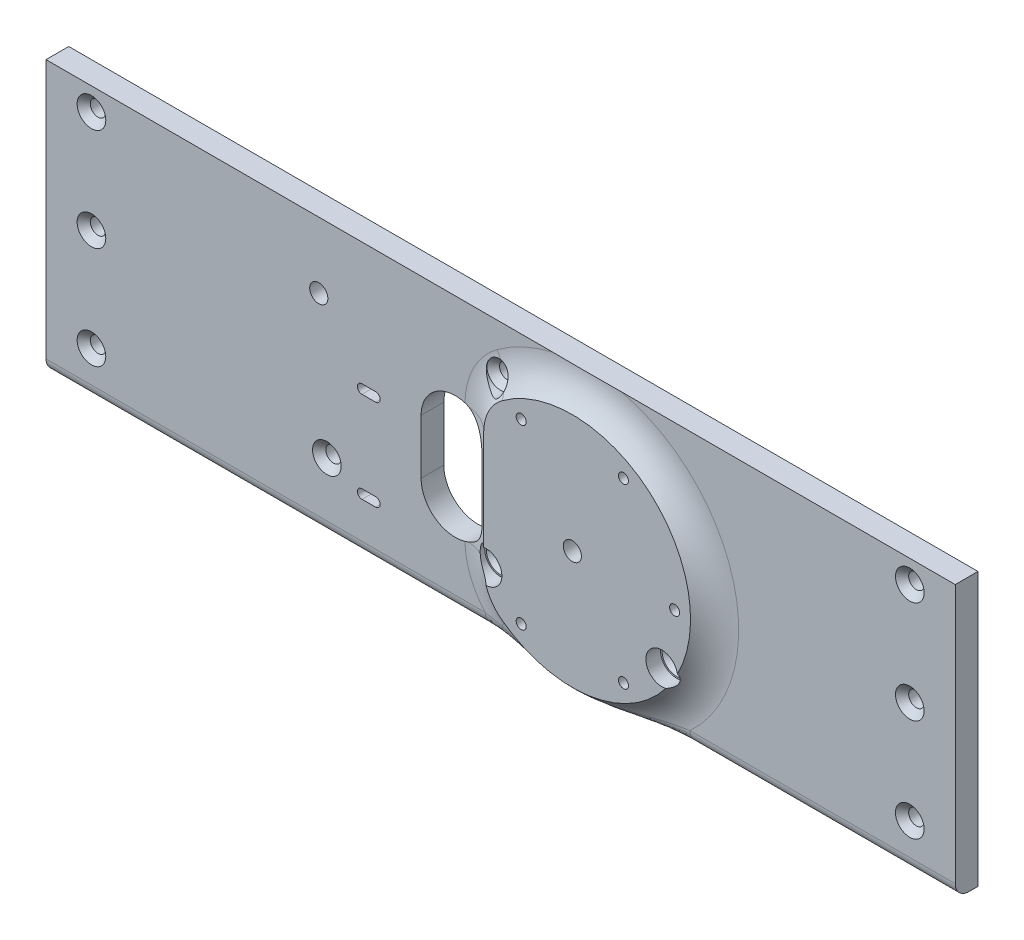
SolidWorks part; units mm, degrees
ref_plane "Front Plane" through (0, 0, 0) normal (0, 0, 1) x (1, 0, 0)
ref_plane "Top Plane" through (0, 0, 0) normal (0, 1, 0) x (1, 0, 0)
ref_plane "Right Plane" through (0, 0, 0) normal (1, 0, 0) x (0, 0, -1)
sketch "Sketch1" plane through (0, 0, 0) normal (0, 0, 1) x (1, 0, 0)
  line L0 (90, 33.5) -> (90, 21.5) construction
  line L1 (0, 0) -> (200, 0)
  line L2 (0, 0) -> (0, 60)
  line L3 (0, 60) -> (200, 60)
  line L4 (200, 0) -> (200, 60)
  line L5 (97.5, 33.5) -> (97.5, 21.5)
  line L6 (82.5, 33.5) -> (82.5, 21.5)
  line L7 (90, 27.5) -> (119, 27.5) construction
  circle A0 centre (119, 27.5) radius 26.5 construction
  circle A2 centre (119, 27.5) radius 2
  circle A3 centre (60, 45.5) radius 2
  arc A4 (97.5, 33.5) -> (82.5, 33.5) centre (90, 33.5) ccw
  arc A5 (82.5, 21.5) -> (97.5, 21.5) centre (90, 21.5) ccw
  arc A6 (142.525, 27.5) -> (140.475, 27.5) centre (141.5, 27.5) ccw construction
  arc A7 (129.225, 8.0144) -> (131.275, 8.0144) centre (130.25, 8.0144) ccw construction
  arc A8 (106.725, 8.0144) -> (108.775, 8.0144) centre (107.75, 8.0144) ccw construction
  arc A9 (106.725, 46.9856) -> (108.775, 46.9856) centre (107.75, 46.9856) ccw construction
  arc A10 (131.275, 46.9856) -> (129.225, 46.9856) centre (130.25, 46.9856) ccw construction
  arc A11 (142.525, 27.5) -> (140.475, 27.5) centre (141.5, 27.5) ccw construction
  arc A12 (129.225, 8.0144) -> (131.275, 8.0144) centre (130.25, 8.0144) ccw construction
  arc A13 (106.725, 8.0144) -> (108.775, 8.0144) centre (107.75, 8.0144) ccw construction
  arc A14 (106.725, 46.9856) -> (108.775, 46.9856) centre (107.75, 46.9856) ccw construction
  arc A15 (131.275, 46.9856) -> (129.225, 46.9856) centre (130.25, 46.9856) ccw construction
  circle A16 centre (130.25, 46.9856) radius 1.1
  circle A17 centre (141.5, 27.5) radius 1.1
  circle A18 centre (130.25, 8.0144) radius 1.1
  circle A19 centre (107.75, 8.0144) radius 1.1
  circle A20 centre (107.75, 46.9856) radius 1.1
  point P8 (90, 27.5)
  dimension "D1" = 4
  dimension "D2" = 4
  dimension "D5" = 53
  dimension "D9" = 1
  dimension "D12" = 5
  dimension "D13" = 2.2
  dimension "D3" = 59
  dimension "D4" = 18
  dimension "D6" = 60
  dimension "D7" = 200
  dimension "D8" = 60
  dimension "D10" = 12
  dimension "D11" = 15
extrude "Boss-Extrude1" add sketch "Sketch1" along normal blind 5
sketch "Sketch3" plane through (0, 0, 5) normal (0, 0, 1) x (1, 0, 0)
  line L0 (99.5, 40.3744) -> (99.5, 14.6256)
  line L1 (97.5, 21.5) -> (97.5, 33.5) construction
  arc A0 (103.5625, 6.5791) -> (103.5625, 48.4209) centre (119, 27.5) ccw
  arc A1 (99.5, 40.3744) -> (103.5625, 48.4209) centre (109.5, 40.3744) cw
  arc A2 (99.5, 14.6256) -> (103.5625, 6.5791) centre (109.5, 14.6256) ccw
  circle A3 centre (119, 27.5) radius 2 construction
  circle A4 centre (107.75, 8.0144) radius 1.1 construction
  circle A5 centre (130.25, 8.0144) radius 1.1 construction
  circle A6 centre (141.5, 27.5) radius 1.1 construction
  circle A7 centre (130.25, 46.9856) radius 1.1 construction
  circle A8 centre (107.75, 46.9856) radius 1.1 construction
  circle A9 centre (119, 27.5) radius 2
  circle A10 centre (107.75, 8.0144) radius 1.1
  circle A11 centre (130.25, 8.0144) radius 1.1
  circle A12 centre (141.5, 27.5) radius 1.1
  circle A13 centre (130.25, 46.9856) radius 1.1
  circle A14 centre (107.75, 46.9856) radius 1.1
  dimension "D1" = 10
  dimension "D3" = 26
  dimension "D2" = 2
extrude "Boss-Extrude2" add sketch "Sketch3" along normal up to surface (3.23 mm away)
fillet "Fillet1" radius 10 4 edges at (100.5732, 10.1187, 5) (99.5, 27.5, 5) (100.5732, 44.8813, 5) (145, 27.5, 5)
sketch "Sketch4" plane through (0, 0, 5) normal (0, 0, 1) x (1, 0, 0)
  line L0 (69.5, 32) -> (72.5, 32) construction
  line L1 (69.5, 33) -> (72.5, 33)
  line L2 (69.5, 31) -> (72.5, 31)
  line L3 (69.5, 12) -> (72.5, 12) construction
  line L4 (69.5, 13) -> (72.5, 13)
  line L5 (69.5, 11) -> (72.5, 11)
  line L6 (0, 0) -> (100.1154, 0) construction
  line L7 (82.5, 33.5) -> (82.5, 21.5) construction
  arc A0 (69.5, 33) -> (69.5, 31) centre (69.5, 32) ccw
  arc A1 (72.5, 31) -> (72.5, 33) centre (72.5, 32) ccw
  arc A2 (69.5, 13) -> (69.5, 11) centre (69.5, 12) ccw
  arc A3 (72.5, 11) -> (72.5, 13) centre (72.5, 12) ccw
  point P2 (71, 32)
  point P7 (71, 12)
  dimension "D1" = 3
  dimension "D2" = 20
  dimension "D3" = 12
  dimension "D4" = 10
  dimension "D5" = 2
extrude "Cut-Extrude1" cut sketch "Sketch4" against normal blind 10
sketch "Sketch8" plane through (0, 0, 5) normal (0, 0, 1) x (1, 0, 0)
  line L0 (10, 55) -> (190, 55) construction
  line L1 (100, 50) -> (100, 60) construction
  line L2 (111.4748, 60) -> (0, 60) construction
  line L3 (61.7843, 15) -> (100, 15) construction
  line L4 (100, 15) -> (100, 50) construction
  line L5 (100, 15) -> (138.6766, 15) construction
  circle A0 centre (190, 10) radius 3 construction
  circle A1 centre (190, 32.5) radius 3 construction
  circle A2 centre (190, 55) radius 3 construction
  circle A3 centre (10, 10) radius 3 construction
  circle A4 centre (10, 32.5) radius 3 construction
  circle A5 centre (10, 55) radius 3 construction
  circle A6 centre (190, 10) radius 3
  circle A7 centre (190, 32.5) radius 3
  circle A8 centre (190, 55) radius 3
  circle A9 centre (10, 10) radius 3
  circle A10 centre (10, 32.5) radius 3
  circle A11 centre (10, 55) radius 3
  circle A12 centre (138.6766, 15) radius 2.1 construction
  circle A13 centre (61.7843, 15) radius 3 construction
  circle A14 centre (138.6766, 15) radius 2.1
  circle A15 centre (61.7843, 15) radius 3
  circle A16 centre (100, 15) radius 3
  circle A17 centre (100, 50) radius 3 construction
  circle A18 centre (100, 50) radius 2.1 construction
  circle A19 centre (100, 50) radius 2.1
  point P31 (0, 0)
  point P32 (101.1096, 53.6973)
  point P36 (100, 49.6918)
hole_wizard "CSK for M3 Flat Head Machine Screw1" positions "3DSketch1" profile "Sketch9" countersink size "M3" standard "ANSI Metric" end condition through all
sketch3d "3DSketch1"
  line L0 (61.7843, 15, 5) -> (100, 15, 5) construction
  line L1 (100, 15, 5) -> (100, 50, 5) construction
  point P0 (10, 55, 5)
  point P3 (10, 32.5, 5)
  point P6 (10, 10, 5)
  point P9 (61.7843, 15, 5)
  point P12 (190, 10, 5)
  point P15 (190, 32.5, 5)
  point P18 (190, 55, 5)
  point P22 (138.6766, 15, 5)
  point P25 (100, 15, 5)
  point P37 (100, 50, 5)
sketch "Sketch9" plane through (10, 55, 5) normal (1, 0, 0) x (0, -1, 0)
  line L0 (0, 0) -> (0, 5)
  line L1 (0, 5) -> (1.7, 5)
  line L2 (1.7, 5) -> (1.7, 1.45)
  line L3 (1.7, 1.45) -> (3.15, 0)
  line L5 (3.15, 0) -> (0, 0)
  line L6 (-1.7, 1.45) -> (-3.15, 0) construction
  line L11 (0, -6.35) -> (0, 107.95) construction
  dimension "Thru Hole Dia." = 3.4
  dimension "Thru Hole Depth" = 5
  dimension "Near C'Sink Dia." = 6.3
  dimension "Near C'Sink Angle" = 90
sketch "Sketch10" plane through (0, 0, 5) normal (0, 0, 1) x (1, 0, 0)
  circle A0 centre (138.6766, 15) radius 3.5
  circle A1 centre (100, 15) radius 3.5
  circle A5 centre (100, 50) radius 3
  point P7 (100, 50)
  dimension "D1" = 7
  dimension "D2" = 6
extrude "Cut-Extrude2" cut sketch "Sketch10" along normal through all
fillet "Fillet2" radius 3 3 edges at (50.0577, 0, 5) (127.8846, 0, 6.0498) (168.9423, 0, 5)
